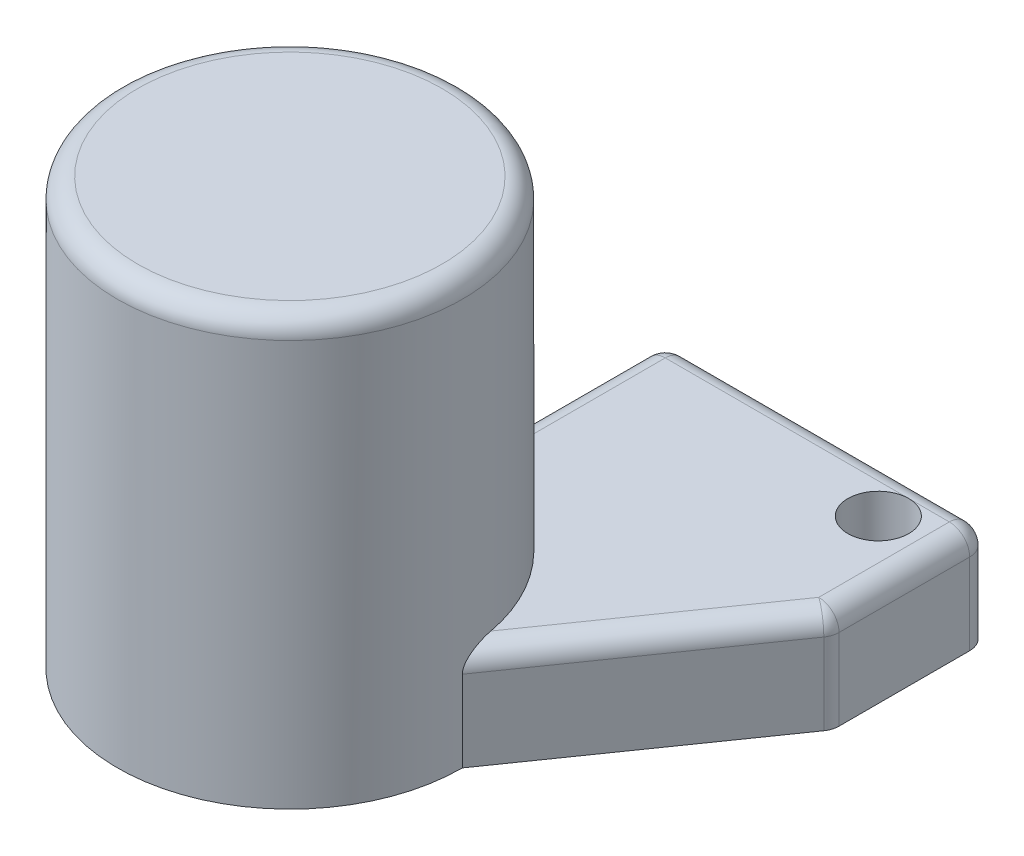
SolidWorks part; units mm, degrees
ref_plane "Alzado" through (0, 0, 0) normal (0, 0, 1) x (1, 0, 0)
ref_plane "Planta" through (0, 0, 0) normal (0, 1, 0) x (1, 0, 0)
ref_plane "Vista lateral" through (0, 0, 0) normal (1, 0, 0) x (0, 0, -1)
sketch "Croquis1" plane through (0, 0, 0) normal (0, 0, 1) x (1, 0, 0)
  line L0 (0, 0) -> (0, 19) construction
  line L1 (0, 19) -> (-6.5, 19)
  line L2 (-6.5, 19) -> (-6.5, 0)
  line L3 (-6.5, 0) -> (-8.5, 0)
  line L4 (-8.5, 0) -> (-8.5, 21)
  line L5 (-8.5, 21) -> (0, 21)
  line L6 (0, 21) -> (0, 19)
  dimension "D1" = 19
  dimension "D2" = 6.5
  dimension "D3" = 2
  dimension "D4" = 2
revolve "Revolución1" add sketch "Croquis1" angle 360 about L0
sketch "Croquis2" plane through (0, 0, 0) normal (0, -1, 0) x (1, 0, 0)
  line L2 (10, -18.5) -> (16, -18.5)
  line L5 (10, -18.5) -> (0, -18.5)
  line L6 (0, -18.5) -> (0, -8.5)
  line L7 (16, -10.75) -> (8.5, 0)
  line L8 (16, -18.5) -> (16, -10.75)
  circle A1 centre (0, 0) radius 8.5 construction
  circle A3 centre (13, -16) radius 1.5
  arc A4 (8.5, 0) -> (0, -8.5) centre (0, 0) cw
  dimension "D1" = 4.5
  dimension "D5" = 3
  dimension "D2" = 16
  dimension "D3" = 7.5
  dimension "D4" = 2.5
  dimension "D6" = 6
extrude "Saliente-Extruir1" add sketch "Croquis2" against normal blind 5
fillet "Redondeo1" radius 1 8 edges at (8, 5, -18.5) (0, 21, -8.5) (16, 2.5, -10.75) (16, 2.5, -18.5) (0, 2.5, -18.5) (0, 5, -13.5) (12.25, 5, -5.375) (16, 5, -14.625)
